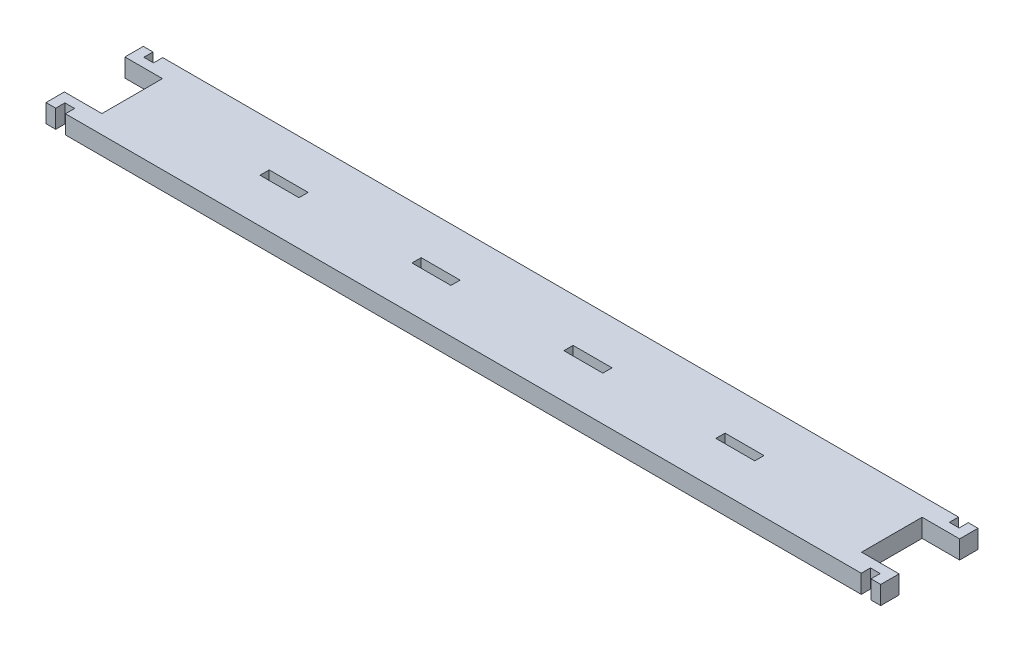
SolidWorks part; units mm, degrees
ref_plane "Front Plane" through (0, 0, 0) normal (0, 0, 1) x (1, 0, 0)
ref_plane "Top Plane" through (0, 0, 0) normal (0, 1, 0) x (1, 0, 0)
ref_plane "Right Plane" through (0, 0, 0) normal (1, 0, 0) x (0, 0, -1)
sketch "Sketch1" plane through (0, 0, 0) normal (0, 1, 0) x (1, 0, 0)
  line L1 (-123.952, 15.875) -> (123.952, 15.875)
  line L2 (-123.952, 15.875) -> (-123.952, -15.875)
  line L3 (-123.952, -15.875) -> (123.952, -15.875)
  line L4 (123.952, 15.875) -> (123.952, -15.875)
  line L5 (-123.952, 15.875) -> (123.952, -15.875) construction
  line L6 (-123.952, -15.875) -> (123.952, 15.875) construction
  point P0 (0, 0)
  dimension "D1" = 247.904
  dimension "D2" = 31.75
extrude "Boss-Extrude1" add sketch "Sketch1" along normal blind 5.9944
sketch "Sketch4" plane through (0, 5.9944, 0) normal (0, 1, 0) x (1, 0, 0)
  line L0 (-123.952, 9.8806) -> (-136.1948, 9.8806)
  line L1 (-123.952, 15.875) -> (-123.952, -15.875) construction
  line L2 (-136.1948, 9.8806) -> (-136.1948, 15.875)
  line L3 (-136.1948, 15.875) -> (-133.0198, 15.875)
  line L4 (-133.0198, 15.875) -> (-133.0198, 12.8778)
  line L5 (-133.0198, 12.8778) -> (-129.8448, 12.8778)
  line L6 (-129.8448, 12.8778) -> (-129.8448, 15.875)
  line L7 (-129.8448, 15.875) -> (-123.952, 15.875)
  line L8 (-123.952, 15.875) -> (-123.952, 9.8806)
  dimension "D1" = 5.8928
  dimension "D2" = 3.175
  dimension "D3" = 3.175
  dimension "D4" = 5.9944
  dimension "D5" = 2.9972
extrude "Boss-Extrude3" add sketch "Sketch4" against normal up to surface (5.9944 mm away) up to face at (0, 0, 0)
mirror "Mirror2" about plane through (0, 0, 0) normal (0, 0, 1) of "Boss-Extrude3" second plane through (0, 0, 0) second plane normal (1, 0, 0)
sketch "Sketch3" plane through (0, 5.9944, 0) normal (0, 1, 0) x (1, 0, 0)
  line L0 (-123.952, 0) -> (123.952, 0) construction
  line L1 (123.952, -9.8806) -> (123.952, 9.8806) construction
  line L2 (-74.3712, -1.4986) -> (-123.952, -1.4986) construction
  line L3 (-80.7212, -1.4986) -> (-68.0212, -1.4986)
  line L4 (-80.7212, -1.4986) -> (-80.7212, 1.4986)
  line L5 (-80.7212, 1.4986) -> (-68.0212, 1.4986)
  line L6 (-68.0212, -1.4986) -> (-68.0212, 1.4986)
  line L7 (-80.7212, -1.4986) -> (-68.0212, 1.4986) construction
  line L8 (-80.7212, 1.4986) -> (-68.0212, -1.4986) construction
  line L9 (-31.1404, -1.4986) -> (-18.4404, -1.4986)
  line L10 (-31.1404, -1.4986) -> (-31.1404, 1.4986)
  line L11 (-31.1404, 1.4986) -> (-18.4404, 1.4986)
  line L12 (-18.4404, -1.4986) -> (-18.4404, 1.4986)
  line L13 (-31.1404, -1.4986) -> (-18.4404, 1.4986) construction
  line L14 (-31.1404, 1.4986) -> (-18.4404, -1.4986) construction
  line L15 (18.4404, -1.4986) -> (31.1404, -1.4986)
  line L16 (18.4404, -1.4986) -> (18.4404, 1.4986)
  line L17 (18.4404, 1.4986) -> (31.1404, 1.4986)
  line L18 (31.1404, -1.4986) -> (31.1404, 1.4986)
  line L19 (18.4404, -1.4986) -> (31.1404, 1.4986) construction
  line L20 (18.4404, 1.4986) -> (31.1404, -1.4986) construction
  line L21 (68.0212, -1.4986) -> (80.7212, -1.4986)
  line L22 (68.0212, -1.4986) -> (68.0212, 1.4986)
  line L23 (68.0212, 1.4986) -> (80.7212, 1.4986)
  line L24 (80.7212, -1.4986) -> (80.7212, 1.4986)
  line L25 (68.0212, -1.4986) -> (80.7212, 1.4986) construction
  line L26 (68.0212, 1.4986) -> (80.7212, -1.4986) construction
  line L27 (-123.952, 9.8806) -> (-123.952, -9.8806) construction
  line L28 (-74.3712, -1.4986) -> (-24.7904, -1.4986) construction
  line L29 (-24.7904, -1.4986) -> (24.7904, -1.4986) construction
  line L30 (24.7904, -1.4986) -> (74.3712, -1.4986) construction
  line L31 (74.3712, -1.4986) -> (123.952, -1.4986) construction
  point P0 (-74.3712, 0)
  point P3 (-24.7904, 0)
  point P6 (0, 0)
  point P16 (24.7904, 0)
  point P21 (74.3712, 0)
  point P33 (24.7904, -1.4986)
  dimension "D2" = 2.9972
  dimension "D3" = 12.7
extrude "Cut-Extrude1" cut sketch "Sketch3" against normal through all
